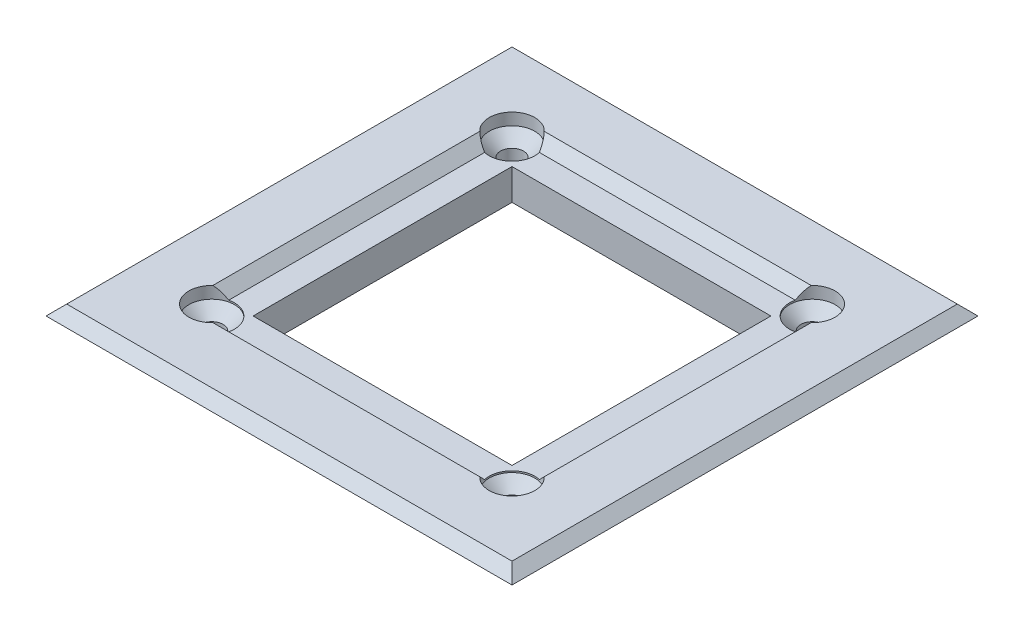
SolidWorks part; units mm, degrees
ref_plane "Front Plane" through (0, 0, 0) normal (0, 0, 1) x (1, 0, 0)
ref_plane "Top Plane" through (0, 0, 0) normal (0, 1, 0) x (1, 0, 0)
ref_plane "Right Plane" through (0, 0, 0) normal (1, 0, 0) x (0, 0, -1)
sketch "Sketch1" plane through (0, 0, 0) normal (0, 1, 0) x (1, 0, 0)
  line L1 (-17.5, -17.5) -> (17.5, -17.5)
  line L2 (-17.5, -17.5) -> (-17.5, 17.5)
  line L3 (-17.5, 17.5) -> (17.5, 17.5)
  line L4 (17.5, -17.5) -> (17.5, 17.5)
  line L5 (-17.5, -17.5) -> (17.5, 17.5) construction
  line L6 (-17.5, 17.5) -> (17.5, -17.5) construction
  point P0 (0, 0)
  dimension "D1" = 35
extrude "Boss-Extrude1" add sketch "Sketch1" along normal blind 3
sketch "Sketch3" plane through (0, 3, 0) normal (0, 1, 0) x (1, 0, 0)
  line L1 (-12.5, -12.5) -> (12.5, -12.5)
  line L2 (-12.5, -12.5) -> (-12.5, 12.5)
  line L3 (-12.5, 12.5) -> (12.5, 12.5)
  line L4 (12.5, -12.5) -> (12.5, 12.5)
  line L5 (-12.5, -12.5) -> (12.5, 12.5) construction
  line L6 (-12.5, 12.5) -> (12.5, -12.5) construction
  point P0 (0, 0)
  dimension "D1" = 25
extrude "Cut-Extrude2" cut sketch "Sketch3" against normal through all
chamfer "Chamfer1" [suppressed] distance 3 angle 45
sketch "Sketch4" plane through (0, 3, 0) normal (0, 1, 0) x (1, 0, 0)
  line L1 (-15, -15) -> (15, -15)
  line L2 (-15, -15) -> (-15, 15)
  line L3 (-15, 15) -> (15, 15)
  line L4 (15, -15) -> (15, 15)
  line L5 (-15, -15) -> (15, 15) construction
  line L6 (-15, 15) -> (15, -15) construction
  line L7 (-22.5, -22.5) -> (22.5, -22.5)
  line L8 (-22.5, -22.5) -> (-22.5, 22.5)
  line L9 (-22.5, 22.5) -> (22.5, 22.5)
  line L10 (22.5, -22.5) -> (22.5, 22.5)
  line L11 (-22.5, -22.5) -> (22.5, 22.5) construction
  line L12 (-22.5, 22.5) -> (22.5, -22.5) construction
  point P0 (0, 0)
  point P6 (0, 0)
  dimension "D1" = 45
  dimension "D2" = 30
extrude "Boss-Extrude2" add sketch "Sketch4" along normal blind 1
chamfer "Chamfer2" distance 1 angle 45 8 edges at (0, 4, -15) (-15, 4, 0) (0, 4, 15) (15, 4, 0) (0, 4, 22.5) (-22.5, 4, 0) (0, 4, -22.5) (22.5, 4, 0)
hole_wizard "CSK for M2 Flat Head Machine Screw1" positions "Sketch6" profile "Sketch5" countersink size "M2" standard "ANSI Metric"
sketch "Sketch6" plane through (0, 3, 0) normal (0, 1, 0) x (1, 0, 0)
  line L0 (14.5, 14.5) -> (0, 14.5) construction
  line L1 (0, 14.5) -> (0, 0) construction
  line L3 (14.5, -14.5) -> (14.5, 0) construction
  line L4 (14.5, 0) -> (0, 0) construction
  line L5 (-14.5, -14.5) -> (0, -14.5) construction
  line L6 (0, -14.5) -> (0, 0) construction
  line L7 (-14.5, 14.5) -> (-14.5, 0) construction
  line L8 (-14.5, 0) -> (0, 0) construction
  point P0 (14.5, 14.5)
  point P15 (14.5, -14.5)
  point P18 (-14.5, -14.5)
  point P21 (-14.5, 14.5)
  point P24 (0, 0)
  dimension "D1" = 14.5
sketch "Sketch5" plane through (14.5, 3, -14.5) normal (1, 0, 0) x (0, 0, 1)
  line L0 (0, 0) -> (0, 20.6609)
  line L1 (0, 20.6609) -> (1.1, 20)
  line L2 (1.1, 20) -> (1.1, 1.25)
  line L3 (1.1, 1.25) -> (2.2, 0.15)
  line L4 (2.2, 0.15) -> (2.2, 0)
  line L6 (2.2, 0) -> (0, 0)
  line L7 (-1.1, 1.25) -> (-2.2, 0.15) construction
  line L10 (0, 20.6609) -> (-1.1, 20) construction
  line L11 (0, -6.35) -> (0, 107.95) construction
  dimension "Hole Dia." = 2.2
  dimension "Hole Depth" = 20
  dimension "C'Sink Dia." = 4.4
  dimension "C'Sink Angle" = 90
  dimension "Drill Angle" = 118
  dimension "Head Clearance" = 0.15
sketch "Sketch7" plane through (0, 3, 0) normal (0, 1, 0) x (1, 0, 0)
  circle A0 centre (14.5, 14.5) radius 2.2
  arc A2 (12.3576, 15) -> (15, 12.3576) centre (14.5, 14.5) ccw construction
  circle A3 centre (14.5, -14.5) radius 2.2
  circle A4 centre (-14.5, -14.5) radius 2.2
  circle A5 centre (-14.5, 14.5) radius 2.2
  point P14 (0, 0)
extrude "Cut-Extrude3" cut sketch "Sketch7" along normal blind 10
